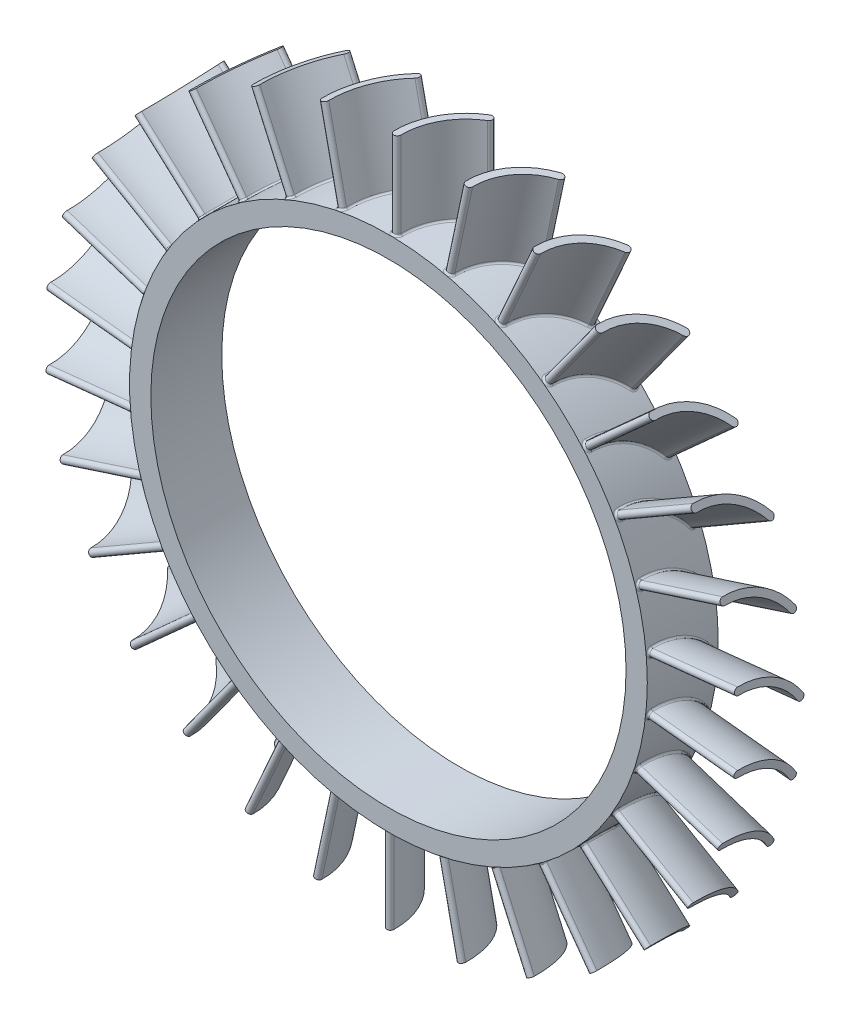
SolidWorks part; units mm, degrees
ref_plane "Front Plane" through (0, 0, 0) normal (0, 0, 1) x (1, 0, 0)
ref_plane "Top Plane" through (0, 0, 0) normal (0, 1, 0) x (1, 0, 0)
ref_plane "Right Plane" through (0, 0, 0) normal (1, 0, 0) x (0, 0, -1)
sketch "Sketch1" plane through (0, 0, 0) normal (0, 0, 1) x (1, 0, 0)
  circle A0 centre (0, 0) radius 73
  circle A1 centre (0, 0) radius 67
  dimension "D1" = 134
  dimension "D2" = 146
extrude "Boss-Extrude1" add sketch "Sketch1" along normal mid plane 20
sketch "Sketch2" plane through (0, 0, 0) normal (0, 1, 0) x (1, 0, 0)
  line L0 (-73, -10) -> (73, -10) construction
  line L1 (67, 10) -> (-67, 10) construction
  arc A0 (-0.0154, -8.5) -> (9.6648, 9) centre (19.9812, -8.1339) cw
  arc A1 (1.9843, -8.4634) -> (10.6964, 7.2866) centre (19.9812, -8.1339) cw
  arc A3 (-0.0154, -8.5) -> (1.9843, -8.4634) centre (0.9844, -8.4817) ccw
  arc A4 (9.6648, 9) -> (10.6964, 7.2866) centre (10.1806, 8.1433) cw
  dimension "D3" = 20
  dimension "D1" = 1.5
  dimension "D2" = 1
  dimension "D4" = 2
extrude "Boss-Extrude2" add sketch "Sketch2" along normal blind 29.5 from offset 68
fillet "Fillet1" radius 0.5 4 edges at (0.8792, 72.9947, 9.4761) (1.2928, 72.9886, 1.0105) (9.2833, 72.4073, -7.7018) (2.4685, 72.9583, 3.9741)
pattern_circular "CirPattern1" count 30 over 360 about axis through (0, 0, 10) along (0, 0, -1) of "Boss-Extrude2", "Fillet1"
